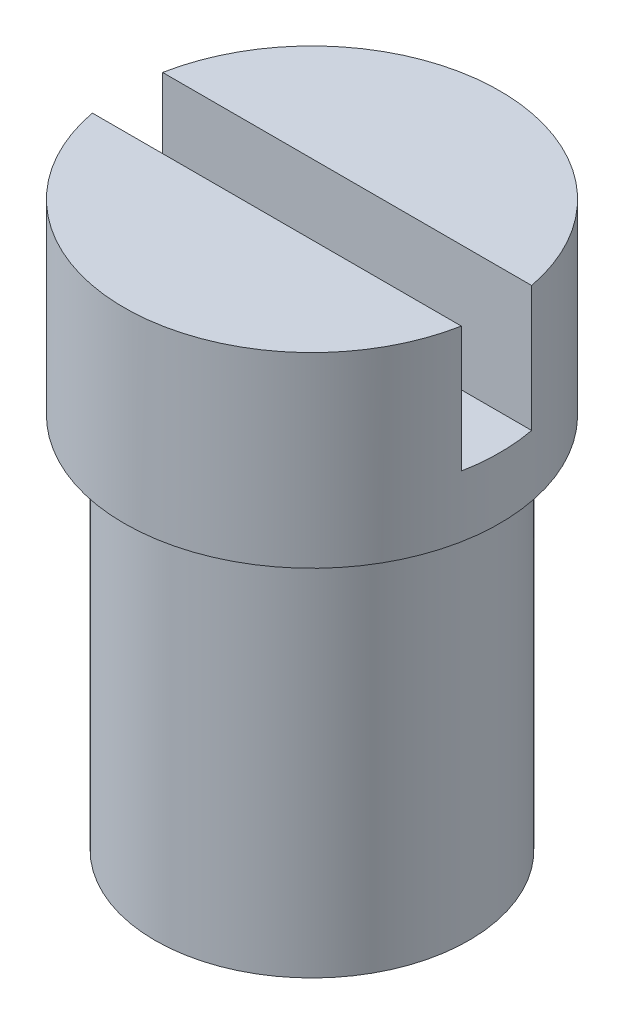
SolidWorks part; units mm, degrees
ref_plane "Front Plane" through (0, 0, 0) normal (0, 0, 1) x (1, 0, 0)
ref_plane "Top Plane" through (0, 0, 0) normal (0, 1, 0) x (1, 0, 0)
ref_plane "Right Plane" through (0, 0, 0) normal (1, 0, 0) x (0, 0, -1)
sketch "Sketch1" plane through (0, 0, 0) normal (0, 1, 0) x (1, 0, 0)
  circle A0 centre (0, 0) radius 2.3749
  dimension "D1" = 4.7498
extrude "Boss-Extrude1" add sketch "Sketch1" along normal blind 2.3622
sketch "Sketch2" plane through (0, 0, 0) normal (0, -1, 0) x (-1, 0, 0)
  circle A0 centre (0, 0) radius 1.9844
  dimension "D1" = 3.9688
extrude "Boss-Extrude2" add sketch "Sketch2" along normal blind 4.7625
sketch "Sketch3" plane through (0, 2.3622, 0) normal (0, 1, 0) x (1, 0, 0)
  line L1 (-2.3749, -0.4445) -> (2.3749, -0.4445)
  line L2 (-2.3749, -0.4445) -> (-2.3749, 0.4445)
  line L3 (-2.3749, 0.4445) -> (2.3749, 0.4445)
  line L4 (2.3749, -0.4445) -> (2.3749, 0.4445)
  line L5 (-2.3749, -0.4445) -> (2.3749, 0.4445) construction
  line L6 (-2.3749, 0.4445) -> (2.3749, -0.4445) construction
  circle A0 centre (0, 0) radius 2.3749 construction
  point P0 (0, 0)
  dimension "D1" = 0.889
extrude "Cut-Extrude1" cut sketch "Sketch3" against normal blind 1.5875
